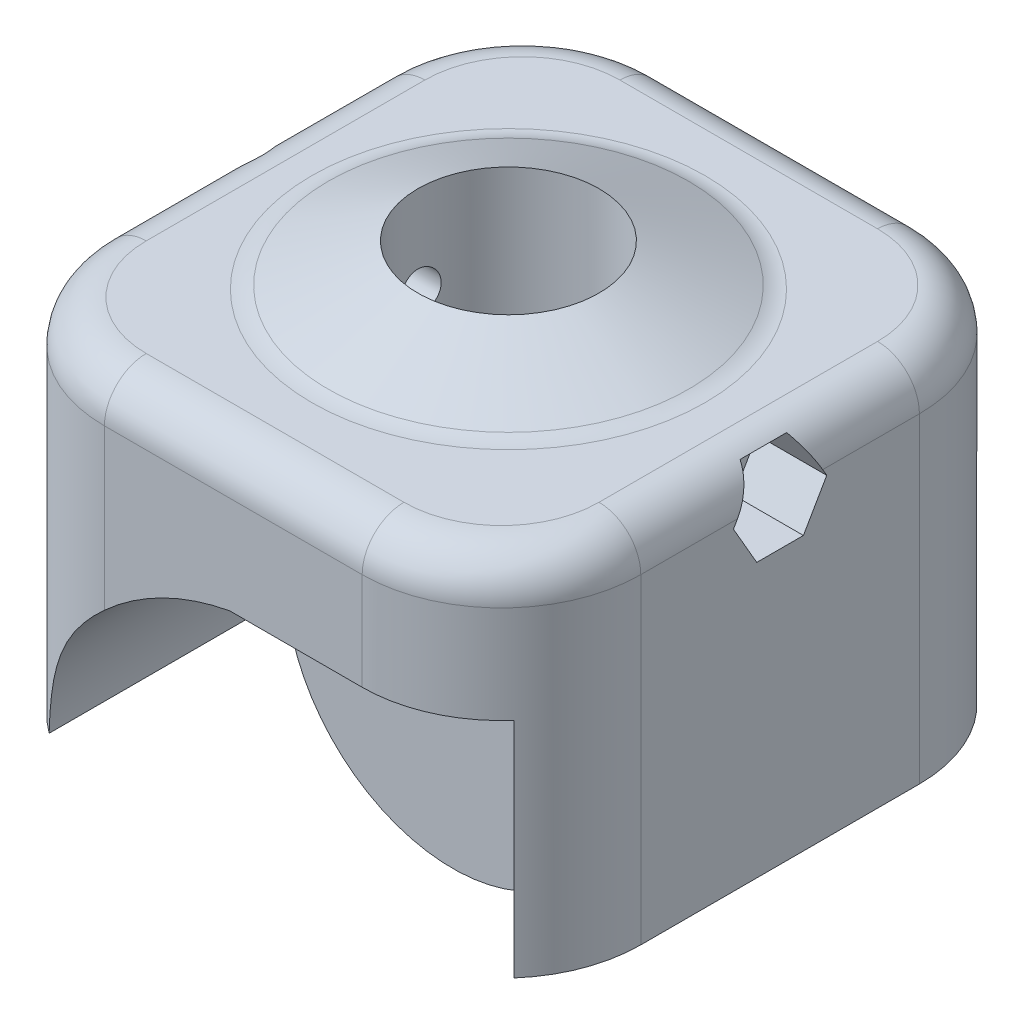
SolidWorks part; units mm, degrees
ref_plane "Alzado" through (0, 0, 0) normal (0, 0, 1) x (1, 0, 0)
ref_plane "Planta" through (0, 0, 0) normal (0, 1, 0) x (1, 0, 0)
ref_plane "Vista lateral" through (0, 0, 0) normal (1, 0, 0) x (0, 0, -1)
sketch "Croquis1" plane through (0, 0, 0) normal (0, 0, 1) x (1, 0, 0)
  line L0 (0, 29.9115) -> (0, -26.2943) construction
  line L1 (-15, 15) -> (15, 15) construction
  line L2 (-15, 15) -> (-15, -15) construction
  line L3 (-15, -15) -> (15, -15) construction
  line L4 (15, 15) -> (15, -15) construction
  line L5 (26.8972, 0) -> (-27.0827, 0) construction
  line L6 (3.32, 27.6693) -> (3.32, -30.0316) construction
  line L7 (23.2997, -6) -> (-25.4019, -6) construction
  line L8 (-25.4019, -4) -> (25.6714, -4) construction
  line L9 (-14.8905, -4) -> (-19, -4)
  line L10 (-19, -4) -> (-19, 22.0167)
  line L11 (-19, 22.0167) -> (17, 22.0167)
  line L12 (17, 22.0167) -> (17, 12.0167)
  line L13 (17, 12.0167) -> (0, 12.0167)
  line L14 (17, 22.0167) -> (19.5, 22.0167)
  line L15 (19.5, 22.0167) -> (19.5, -4)
  line L16 (19.5, -4) -> (17, -4)
  line L17 (17, -4) -> (17, 12.0167)
  circle A0 centre (0, 0) radius 2.3813
  arc A1 (0.1812, 11.0332) -> (3.32, -23.32) centre (3.32, -6) ccw construction
  arc A2 (0, 12.0167) -> (3.32, -24.32) centre (3.32, -6) ccw
  dimension "D1" = 4.7625
  dimension "D10" = 17.32
  dimension "D2" = 30
  dimension "D3" = 30
  dimension "D4" = 3.32
  dimension "D5" = 6
  dimension "D6" = 4
  dimension "D8" = 10
  dimension "D9" = 19
  dimension "D11" = 36
  dimension "D12" = 2.5
  dimension "D7" = 1
extrude "Saliente-Extruir1" add sketch "Croquis1" along normal mid plane 40 contours A2 L13 L12 L11 L10 L9 | L17 L16 L15 L14 L12 region at (-4.4791, 14.0823, 0) region at (18.25, 9.0083, 0)
sketch "Croquis2" plane through (0, 0, 0) normal (0, 0, 1) x (1, 0, 0)
  circle A0 centre (0, 0) radius 2.3813
  circle A1 centre (0, 0) radius 12
  dimension "D1" = 4.7625
  dimension "D2" = 24
extrude "Saliente-Extruir2" add sketch "Croquis2" along normal mid plane 8
sketch "Croquis3" plane through (0, 22.0167, 0) normal (0, 1, 0) x (1, 0, 0)
  circle A0 centre (0, 0) radius 6.5
  dimension "D1" = 13
extrude "Cortar-Extruir1" cut sketch "Croquis3" against normal blind 7
sketch "Croquis4" plane through (0, 0, 0) normal (0, 0, 1) x (1, 0, 0)
  line L0 (0, -1.3197) -> (0, 38.8808) construction
  line L1 (6.5, 25.0167) -> (6.5, 22.0167)
  line L2 (-19, 22.0167) -> (19.5, 22.0167) construction
  line L3 (6.5, 22.0167) -> (13.5, 22.0167)
  line L4 (13.5, 22.0167) -> (6.5, 25.0167)
  dimension "D1" = 6.5
  dimension "D2" = 7
  dimension "D3" = 3
revolve "Revolución1" add sketch "Croquis4" angle 360 about L0
fillet "Redondeo4" radius 10 2 edges at (-19, 9.0083, -20) (-19, 9.0083, 20)
fillet "Redondeo5" radius 10 2 edges at (19.5, 9.0083, -20) (19.5, 9.0083, 20)
sketch "Croquis5" plane through (-19, 0, 0) normal (-1, 0, 0) x (0, 0, 1)
  line L0 (33.2128, 0) -> (-25.2986, 0) construction
  line L1 (0, 34.6333) -> (0, -9.0144) construction
  line L2 (6.5, 15.0167) -> (-6.5, 15.0167) construction
  circle A0 centre (0, 18.5167) radius 1.5
  dimension "D1" = 3
  dimension "D2" = 3.5
extrude "Cortar-Extruir2" cut sketch "Croquis5" against normal blind 50
sketch "Croquis6" plane through (-19, 0, 0) normal (-1, 0, 0) x (0, 0, 1)
  circle A1 centre (0, 18.5167) radius 3
  dimension "D1" = 6
extrude "Cortar-Extruir3" cut sketch "Croquis6" against normal blind 6
sketch "Croquis7" plane through (19.5, 0, 0) normal (1, 0, 0) x (0, 0, -1)
  line L1 (1.6743, 21.4167) -> (-1.6743, 21.4167)
  line L2 (-1.6743, 21.4167) -> (-3.3486, 18.5167)
  line L3 (-3.3486, 18.5167) -> (-1.6743, 15.6167)
  line L4 (-1.6743, 15.6167) -> (1.6743, 15.6167)
  line L5 (1.6743, 15.6167) -> (3.3486, 18.5167)
  line L6 (3.3486, 18.5167) -> (1.6743, 21.4167)
  circle A0 centre (0, 18.5167) radius 2.9 construction
  dimension "D1" = 5.8
extrude "Cortar-Extruir4" cut sketch "Croquis7" against normal blind 5
fillet "Redondeo6" radius 3 8 edges at (-16.0711, 22.0167, 17.0711) (-19, 22.0167, 0) (-16.0711, 22.0167, -17.0711) (0.25, 22.0167, -20) (16.5711, 22.0167, -17.0711) (19.5, 22.0167, 0) (16.5711, 22.0167, 17.0711) (0.25, 22.0167, 20)
fillet "Redondeo7" radius 3 1 edges at (-13.5, 22.0167, 0)
